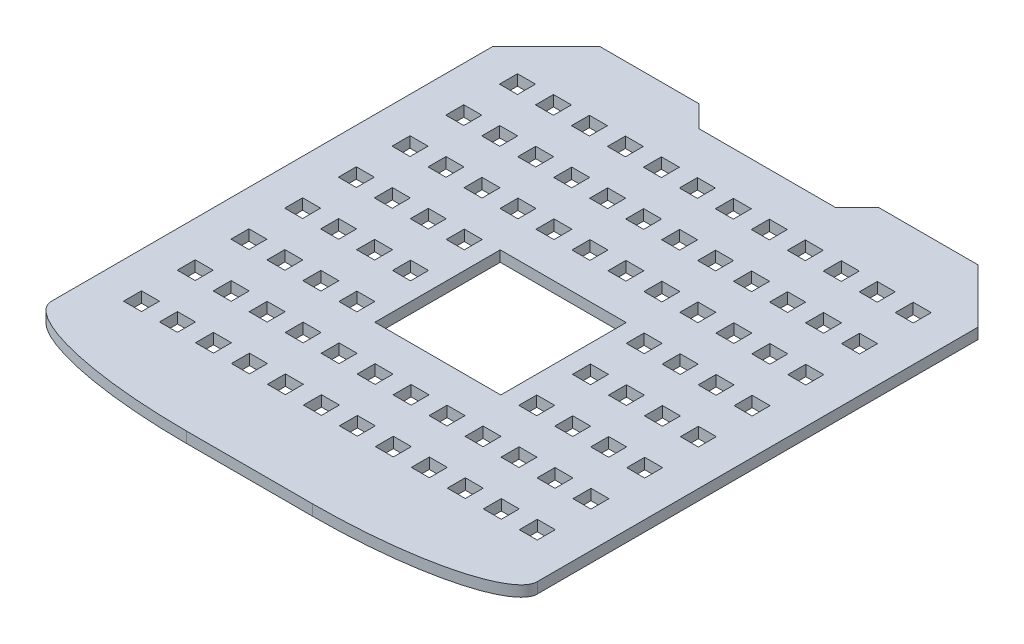
SolidWorks part; units mm, degrees
material "Balsa"
ref_plane "Front Plane" through (0, 0, 0) normal (0, 0, 1) x (1, 0, 0)
ref_plane "Top Plane" through (0, 0, 0) normal (0, 1, 0) x (1, 0, 0)
ref_plane "Right Plane" through (0, 0, 0) normal (1, 0, 0) x (0, 0, -1)
sketch "Sketch1" plane through (0, 0, 0) normal (0, 1, 0) x (1, 0, 0)
  line L1 (-67.5, 75) -> (67.5, 75)
  line L2 (-67.5, 75) -> (-67.5, -75)
  line L3 (-67.5, -75) -> (67.5, -75)
  line L4 (67.5, 75) -> (67.5, -75)
  line L5 (-67.5, 75) -> (67.5, -75) construction
  line L6 (-67.5, -75) -> (67.5, 75) construction
  point P0 (0, 0)
  dimension "D1" = 135
  dimension "D2" = 150
extrude "Boss-Extrude1" add sketch "Sketch1" along normal blind 3
sketch "Sketch2" plane through (0, 3, 0) normal (0, 1, 0) x (1, 0, 0)
  line L0 (-67.5, 75) -> (-67.5, -75) construction
  line L1 (-57.5, 52) -> (-52.5, 52)
  line L2 (-57.5, 52) -> (-57.5, 57)
  line L3 (-57.5, 57) -> (-52.5, 57)
  line L4 (-52.5, 52) -> (-52.5, 57)
  line L5 (-57.5, 52) -> (-52.5, 57) construction
  line L6 (-57.5, 57) -> (-52.5, 52) construction
  line L7 (67.5, 75) -> (-67.5, 75) construction
  line L732 (-47.5, 52) -> (-47.5, 57)
  line L733 (-47.5, 52) -> (-42.5, 52)
  line L734 (-42.5, 52) -> (-42.5, 57)
  line L735 (-47.5, 57) -> (-42.5, 57)
  line L736 (-37.5, 52) -> (-37.5, 57)
  line L737 (-37.5, 52) -> (-32.5, 52)
  line L738 (-32.5, 52) -> (-32.5, 57)
  line L739 (-37.5, 57) -> (-32.5, 57)
  line L740 (-27.5, 52) -> (-27.5, 57)
  line L741 (-27.5, 52) -> (-22.5, 52)
  line L742 (-22.5, 52) -> (-22.5, 57)
  line L743 (-27.5, 57) -> (-22.5, 57)
  line L744 (-17.5, 52) -> (-17.5, 57)
  line L745 (-17.5, 52) -> (-12.5, 52)
  line L746 (-12.5, 52) -> (-12.5, 57)
  line L747 (-17.5, 57) -> (-12.5, 57)
  line L748 (-7.5, 52) -> (-7.5, 57)
  line L749 (-7.5, 52) -> (-2.5, 52)
  line L750 (-2.5, 52) -> (-2.5, 57)
  line L751 (-7.5, 57) -> (-2.5, 57)
  line L752 (2.5, 52) -> (2.5, 57)
  line L753 (2.5, 52) -> (7.5, 52)
  line L754 (7.5, 52) -> (7.5, 57)
  line L755 (2.5, 57) -> (7.5, 57)
  line L756 (12.5, 52) -> (12.5, 57)
  line L757 (12.5, 52) -> (17.5, 52)
  line L758 (17.5, 52) -> (17.5, 57)
  line L759 (12.5, 57) -> (17.5, 57)
  line L760 (22.5, 52) -> (22.5, 57)
  line L761 (22.5, 52) -> (27.5, 52)
  line L762 (27.5, 52) -> (27.5, 57)
  line L763 (22.5, 57) -> (27.5, 57)
  line L764 (32.5, 52) -> (32.5, 57)
  line L765 (32.5, 52) -> (37.5, 52)
  line L766 (37.5, 52) -> (37.5, 57)
  line L767 (32.5, 57) -> (37.5, 57)
  line L768 (42.5, 52) -> (42.5, 57)
  line L769 (42.5, 52) -> (47.5, 52)
  line L770 (47.5, 52) -> (47.5, 57)
  line L771 (42.5, 57) -> (47.5, 57)
  line L772 (52.5, 52) -> (52.5, 57)
  line L773 (52.5, 52) -> (57.5, 52)
  line L774 (57.5, 52) -> (57.5, 57)
  line L775 (52.5, 57) -> (57.5, 57)
  line L780 (-47.5, 37.0714) -> (-47.5, 42.0714)
  line L781 (-47.5, 37.0714) -> (-42.5, 37.0714)
  line L782 (-42.5, 37.0714) -> (-42.5, 42.0714)
  line L783 (-47.5, 42.0714) -> (-42.5, 42.0714)
  line L784 (-37.5, 37.0714) -> (-37.5, 42.0714)
  line L785 (-37.5, 37.0714) -> (-32.5, 37.0714)
  line L786 (-32.5, 37.0714) -> (-32.5, 42.0714)
  line L787 (-37.5, 42.0714) -> (-32.5, 42.0714)
  line L788 (-27.5, 37.0714) -> (-27.5, 42.0714)
  line L789 (-27.5, 37.0714) -> (-22.5, 37.0714)
  line L790 (-22.5, 37.0714) -> (-22.5, 42.0714)
  line L791 (-27.5, 42.0714) -> (-22.5, 42.0714)
  line L792 (-17.5, 37.0714) -> (-17.5, 42.0714)
  line L793 (-17.5, 37.0714) -> (-12.5, 37.0714)
  line L794 (-12.5, 37.0714) -> (-12.5, 42.0714)
  line L795 (-17.5, 42.0714) -> (-12.5, 42.0714)
  line L796 (-7.5, 37.0714) -> (-7.5, 42.0714)
  line L797 (-7.5, 37.0714) -> (-2.5, 37.0714)
  line L798 (-2.5, 37.0714) -> (-2.5, 42.0714)
  line L799 (-7.5, 42.0714) -> (-2.5, 42.0714)
  line L800 (2.5, 37.0714) -> (2.5, 42.0714)
  line L801 (2.5, 37.0714) -> (7.5, 37.0714)
  line L802 (7.5, 37.0714) -> (7.5, 42.0714)
  line L803 (2.5, 42.0714) -> (7.5, 42.0714)
  line L804 (12.5, 37.0714) -> (12.5, 42.0714)
  line L805 (12.5, 37.0714) -> (17.5, 37.0714)
  line L806 (17.5, 37.0714) -> (17.5, 42.0714)
  line L807 (12.5, 42.0714) -> (17.5, 42.0714)
  line L808 (22.5, 37.0714) -> (22.5, 42.0714)
  line L809 (22.5, 37.0714) -> (27.5, 37.0714)
  line L810 (27.5, 37.0714) -> (27.5, 42.0714)
  line L811 (22.5, 42.0714) -> (27.5, 42.0714)
  line L812 (32.5, 37.0714) -> (32.5, 42.0714)
  line L813 (32.5, 37.0714) -> (37.5, 37.0714)
  line L814 (37.5, 37.0714) -> (37.5, 42.0714)
  line L815 (32.5, 42.0714) -> (37.5, 42.0714)
  line L816 (42.5, 37.0714) -> (42.5, 42.0714)
  line L817 (42.5, 37.0714) -> (47.5, 37.0714)
  line L818 (47.5, 37.0714) -> (47.5, 42.0714)
  line L819 (42.5, 42.0714) -> (47.5, 42.0714)
  line L820 (52.5, 37.0714) -> (52.5, 42.0714)
  line L821 (52.5, 37.0714) -> (57.5, 37.0714)
  line L822 (57.5, 37.0714) -> (57.5, 42.0714)
  line L823 (52.5, 42.0714) -> (57.5, 42.0714)
  line L828 (-47.5, 22.1429) -> (-47.5, 27.1429)
  line L829 (-47.5, 22.1429) -> (-42.5, 22.1429)
  line L830 (-42.5, 22.1429) -> (-42.5, 27.1429)
  line L831 (-47.5, 27.1429) -> (-42.5, 27.1429)
  line L832 (-37.5, 22.1429) -> (-37.5, 27.1429)
  line L833 (-37.5, 22.1429) -> (-32.5, 22.1429)
  line L834 (-32.5, 22.1429) -> (-32.5, 27.1429)
  line L835 (-37.5, 27.1429) -> (-32.5, 27.1429)
  line L836 (-27.5, 22.1429) -> (-27.5, 27.1429)
  line L837 (-27.5, 22.1429) -> (-22.5, 22.1429)
  line L838 (-22.5, 22.1429) -> (-22.5, 27.1429)
  line L839 (-27.5, 27.1429) -> (-22.5, 27.1429)
  line L840 (-17.5, 22.1429) -> (-17.5, 27.1429)
  line L841 (-17.5, 22.1429) -> (-12.5, 22.1429)
  line L842 (-12.5, 22.1429) -> (-12.5, 27.1429)
  line L843 (-17.5, 27.1429) -> (-12.5, 27.1429)
  line L844 (-7.5, 22.1429) -> (-7.5, 27.1429)
  line L845 (-7.5, 22.1429) -> (-2.5, 22.1429)
  line L846 (-2.5, 22.1429) -> (-2.5, 27.1429)
  line L847 (-7.5, 27.1429) -> (-2.5, 27.1429)
  line L848 (2.5, 22.1429) -> (2.5, 27.1429)
  line L849 (2.5, 22.1429) -> (7.5, 22.1429)
  line L850 (7.5, 22.1429) -> (7.5, 27.1429)
  line L851 (2.5, 27.1429) -> (7.5, 27.1429)
  line L852 (12.5, 22.1429) -> (12.5, 27.1429)
  line L853 (12.5, 22.1429) -> (17.5, 22.1429)
  line L854 (17.5, 22.1429) -> (17.5, 27.1429)
  line L855 (12.5, 27.1429) -> (17.5, 27.1429)
  line L856 (22.5, 22.1429) -> (22.5, 27.1429)
  line L857 (22.5, 22.1429) -> (27.5, 22.1429)
  line L858 (27.5, 22.1429) -> (27.5, 27.1429)
  line L859 (22.5, 27.1429) -> (27.5, 27.1429)
  line L860 (32.5, 22.1429) -> (32.5, 27.1429)
  line L861 (32.5, 22.1429) -> (37.5, 22.1429)
  line L862 (37.5, 22.1429) -> (37.5, 27.1429)
  line L863 (32.5, 27.1429) -> (37.5, 27.1429)
  line L864 (42.5, 22.1429) -> (42.5, 27.1429)
  line L865 (42.5, 22.1429) -> (47.5, 22.1429)
  line L866 (47.5, 22.1429) -> (47.5, 27.1429)
  line L867 (42.5, 27.1429) -> (47.5, 27.1429)
  line L868 (52.5, 22.1429) -> (52.5, 27.1429)
  line L869 (52.5, 22.1429) -> (57.5, 22.1429)
  line L870 (57.5, 22.1429) -> (57.5, 27.1429)
  line L871 (52.5, 27.1429) -> (57.5, 27.1429)
  line L876 (-47.5, 7.2143) -> (-47.5, 12.2143)
  line L877 (-47.5, 7.2143) -> (-42.5, 7.2143)
  line L878 (-42.5, 7.2143) -> (-42.5, 12.2143)
  line L879 (-47.5, 12.2143) -> (-42.5, 12.2143)
  line L880 (-37.5, 7.2143) -> (-37.5, 12.2143)
  line L881 (-37.5, 7.2143) -> (-32.5, 7.2143)
  line L882 (-32.5, 7.2143) -> (-32.5, 12.2143)
  line L883 (-37.5, 12.2143) -> (-32.5, 12.2143)
  line L884 (-27.5, 7.2143) -> (-27.5, 12.2143)
  line L885 (-27.5, 7.2143) -> (-22.5, 7.2143)
  line L886 (-22.5, 7.2143) -> (-22.5, 12.2143)
  line L887 (-27.5, 12.2143) -> (-22.5, 12.2143)
  line L888 (-17.5, 7.2143) -> (-17.5, 12.2143)
  line L889 (-17.5, 7.2143) -> (-12.5, 7.2143)
  line L890 (-12.5, 7.2143) -> (-12.5, 12.2143)
  line L891 (-17.5, 12.2143) -> (-12.5, 12.2143)
  line L892 (-7.5, 7.2143) -> (-7.5, 12.2143)
  line L893 (-7.5, 7.2143) -> (-2.5, 7.2143)
  line L894 (-2.5, 7.2143) -> (-2.5, 12.2143)
  line L895 (-7.5, 12.2143) -> (-2.5, 12.2143)
  line L896 (2.5, 7.2143) -> (2.5, 12.2143)
  line L897 (2.5, 7.2143) -> (7.5, 7.2143)
  line L898 (7.5, 7.2143) -> (7.5, 12.2143)
  line L899 (2.5, 12.2143) -> (7.5, 12.2143)
  line L900 (12.5, 7.2143) -> (12.5, 12.2143)
  line L901 (12.5, 7.2143) -> (17.5, 7.2143)
  line L902 (17.5, 7.2143) -> (17.5, 12.2143)
  line L903 (12.5, 12.2143) -> (17.5, 12.2143)
  line L904 (22.5, 7.2143) -> (22.5, 12.2143)
  line L905 (22.5, 7.2143) -> (27.5, 7.2143)
  line L906 (27.5, 7.2143) -> (27.5, 12.2143)
  line L907 (22.5, 12.2143) -> (27.5, 12.2143)
  line L908 (32.5, 7.2143) -> (32.5, 12.2143)
  line L909 (32.5, 7.2143) -> (37.5, 7.2143)
  line L910 (37.5, 7.2143) -> (37.5, 12.2143)
  line L911 (32.5, 12.2143) -> (37.5, 12.2143)
  line L912 (42.5, 7.2143) -> (42.5, 12.2143)
  line L913 (42.5, 7.2143) -> (47.5, 7.2143)
  line L914 (47.5, 7.2143) -> (47.5, 12.2143)
  line L915 (42.5, 12.2143) -> (47.5, 12.2143)
  line L916 (52.5, 7.2143) -> (52.5, 12.2143)
  line L917 (52.5, 7.2143) -> (57.5, 7.2143)
  line L918 (57.5, 7.2143) -> (57.5, 12.2143)
  line L919 (52.5, 12.2143) -> (57.5, 12.2143)
  line L924 (-47.5, -7.7143) -> (-47.5, -2.7143)
  line L925 (-47.5, -7.7143) -> (-42.5, -7.7143)
  line L926 (-42.5, -7.7143) -> (-42.5, -2.7143)
  line L927 (-47.5, -2.7143) -> (-42.5, -2.7143)
  line L928 (-37.5, -7.7143) -> (-37.5, -2.7143)
  line L929 (-37.5, -7.7143) -> (-32.5, -7.7143)
  line L930 (-32.5, -7.7143) -> (-32.5, -2.7143)
  line L931 (-37.5, -2.7143) -> (-32.5, -2.7143)
  line L932 (-27.5, -7.7143) -> (-27.5, -2.7143)
  line L933 (-27.5, -7.7143) -> (-22.5, -7.7143)
  line L934 (-22.5, -7.7143) -> (-22.5, -2.7143)
  line L935 (-27.5, -2.7143) -> (-22.5, -2.7143)
  line L936 (-17.5, -7.7143) -> (-17.5, -2.7143)
  line L937 (-17.5, -7.7143) -> (-12.5, -7.7143)
  line L938 (-12.5, -7.7143) -> (-12.5, -2.7143)
  line L939 (-17.5, -2.7143) -> (-12.5, -2.7143)
  line L940 (-7.5, -7.7143) -> (-7.5, -2.7143)
  line L941 (-7.5, -7.7143) -> (-2.5, -7.7143)
  line L942 (-2.5, -7.7143) -> (-2.5, -2.7143)
  line L943 (-7.5, -2.7143) -> (-2.5, -2.7143)
  line L944 (2.5, -7.7143) -> (2.5, -2.7143)
  line L945 (2.5, -7.7143) -> (7.5, -7.7143)
  line L946 (7.5, -7.7143) -> (7.5, -2.7143)
  line L947 (2.5, -2.7143) -> (7.5, -2.7143)
  line L948 (12.5, -7.7143) -> (12.5, -2.7143)
  line L949 (12.5, -7.7143) -> (17.5, -7.7143)
  line L950 (17.5, -7.7143) -> (17.5, -2.7143)
  line L951 (12.5, -2.7143) -> (17.5, -2.7143)
  line L952 (22.5, -7.7143) -> (22.5, -2.7143)
  line L953 (22.5, -7.7143) -> (27.5, -7.7143)
  line L954 (27.5, -7.7143) -> (27.5, -2.7143)
  line L955 (22.5, -2.7143) -> (27.5, -2.7143)
  line L956 (32.5, -7.7143) -> (32.5, -2.7143)
  line L957 (32.5, -7.7143) -> (37.5, -7.7143)
  line L958 (37.5, -7.7143) -> (37.5, -2.7143)
  line L959 (32.5, -2.7143) -> (37.5, -2.7143)
  line L960 (42.5, -7.7143) -> (42.5, -2.7143)
  line L961 (42.5, -7.7143) -> (47.5, -7.7143)
  line L962 (47.5, -7.7143) -> (47.5, -2.7143)
  line L963 (42.5, -2.7143) -> (47.5, -2.7143)
  line L964 (52.5, -7.7143) -> (52.5, -2.7143)
  line L965 (52.5, -7.7143) -> (57.5, -7.7143)
  line L966 (57.5, -7.7143) -> (57.5, -2.7143)
  line L967 (52.5, -2.7143) -> (57.5, -2.7143)
  line L972 (-47.5, -22.6429) -> (-47.5, -17.6429)
  line L973 (-47.5, -22.6429) -> (-42.5, -22.6429)
  line L974 (-42.5, -22.6429) -> (-42.5, -17.6429)
  line L975 (-47.5, -17.6429) -> (-42.5, -17.6429)
  line L976 (-37.5, -22.6429) -> (-37.5, -17.6429)
  line L977 (-37.5, -22.6429) -> (-32.5, -22.6429)
  line L978 (-32.5, -22.6429) -> (-32.5, -17.6429)
  line L979 (-37.5, -17.6429) -> (-32.5, -17.6429)
  line L980 (-27.5, -22.6429) -> (-27.5, -17.6429)
  line L981 (-27.5, -22.6429) -> (-22.5, -22.6429)
  line L982 (-22.5, -22.6429) -> (-22.5, -17.6429)
  line L983 (-27.5, -17.6429) -> (-22.5, -17.6429)
  line L984 (-17.5, -22.6429) -> (-17.5, -17.6429)
  line L985 (-17.5, -22.6429) -> (-12.5, -22.6429)
  line L986 (-12.5, -22.6429) -> (-12.5, -17.6429)
  line L987 (-17.5, -17.6429) -> (-12.5, -17.6429)
  line L988 (-7.5, -22.6429) -> (-7.5, -17.6429)
  line L989 (-7.5, -22.6429) -> (-2.5, -22.6429)
  line L990 (-2.5, -22.6429) -> (-2.5, -17.6429)
  line L991 (-7.5, -17.6429) -> (-2.5, -17.6429)
  line L992 (2.5, -22.6429) -> (2.5, -17.6429)
  line L993 (2.5, -22.6429) -> (7.5, -22.6429)
  line L994 (7.5, -22.6429) -> (7.5, -17.6429)
  line L995 (2.5, -17.6429) -> (7.5, -17.6429)
  line L996 (12.5, -22.6429) -> (12.5, -17.6429)
  line L997 (12.5, -22.6429) -> (17.5, -22.6429)
  line L998 (17.5, -22.6429) -> (17.5, -17.6429)
  line L999 (12.5, -17.6429) -> (17.5, -17.6429)
  line L1000 (22.5, -22.6429) -> (22.5, -17.6429)
  line L1001 (22.5, -22.6429) -> (27.5, -22.6429)
  line L1002 (27.5, -22.6429) -> (27.5, -17.6429)
  line L1003 (22.5, -17.6429) -> (27.5, -17.6429)
  line L1004 (32.5, -22.6429) -> (32.5, -17.6429)
  line L1005 (32.5, -22.6429) -> (37.5, -22.6429)
  line L1006 (37.5, -22.6429) -> (37.5, -17.6429)
  line L1007 (32.5, -17.6429) -> (37.5, -17.6429)
  line L1008 (42.5, -22.6429) -> (42.5, -17.6429)
  line L1009 (42.5, -22.6429) -> (47.5, -22.6429)
  line L1010 (47.5, -22.6429) -> (47.5, -17.6429)
  line L1011 (42.5, -17.6429) -> (47.5, -17.6429)
  line L1012 (52.5, -22.6429) -> (52.5, -17.6429)
  line L1013 (52.5, -22.6429) -> (57.5, -22.6429)
  line L1014 (57.5, -22.6429) -> (57.5, -17.6429)
  line L1015 (52.5, -17.6429) -> (57.5, -17.6429)
  line L1020 (-47.5, -37.5714) -> (-47.5, -32.5714)
  line L1021 (-47.5, -37.5714) -> (-42.5, -37.5714)
  line L1022 (-42.5, -37.5714) -> (-42.5, -32.5714)
  line L1023 (-47.5, -32.5714) -> (-42.5, -32.5714)
  line L1024 (-37.5, -37.5714) -> (-37.5, -32.5714)
  line L1025 (-37.5, -37.5714) -> (-32.5, -37.5714)
  line L1026 (-32.5, -37.5714) -> (-32.5, -32.5714)
  line L1027 (-37.5, -32.5714) -> (-32.5, -32.5714)
  line L1028 (-27.5, -37.5714) -> (-27.5, -32.5714)
  line L1029 (-27.5, -37.5714) -> (-22.5, -37.5714)
  line L1030 (-22.5, -37.5714) -> (-22.5, -32.5714)
  line L1031 (-27.5, -32.5714) -> (-22.5, -32.5714)
  line L1032 (-17.5, -37.5714) -> (-17.5, -32.5714)
  line L1033 (-17.5, -37.5714) -> (-12.5, -37.5714)
  line L1034 (-12.5, -37.5714) -> (-12.5, -32.5714)
  line L1035 (-17.5, -32.5714) -> (-12.5, -32.5714)
  line L1036 (-7.5, -37.5714) -> (-7.5, -32.5714)
  line L1037 (-7.5, -37.5714) -> (-2.5, -37.5714)
  line L1038 (-2.5, -37.5714) -> (-2.5, -32.5714)
  line L1039 (-7.5, -32.5714) -> (-2.5, -32.5714)
  line L1040 (2.5, -37.5714) -> (2.5, -32.5714)
  line L1041 (2.5, -37.5714) -> (7.5, -37.5714)
  line L1042 (7.5, -37.5714) -> (7.5, -32.5714)
  line L1043 (2.5, -32.5714) -> (7.5, -32.5714)
  line L1044 (12.5, -37.5714) -> (12.5, -32.5714)
  line L1045 (12.5, -37.5714) -> (17.5, -37.5714)
  line L1046 (17.5, -37.5714) -> (17.5, -32.5714)
  line L1047 (12.5, -32.5714) -> (17.5, -32.5714)
  line L1048 (22.5, -37.5714) -> (22.5, -32.5714)
  line L1049 (22.5, -37.5714) -> (27.5, -37.5714)
  line L1050 (27.5, -37.5714) -> (27.5, -32.5714)
  line L1051 (22.5, -32.5714) -> (27.5, -32.5714)
  line L1052 (32.5, -37.5714) -> (32.5, -32.5714)
  line L1053 (32.5, -37.5714) -> (37.5, -37.5714)
  line L1054 (37.5, -37.5714) -> (37.5, -32.5714)
  line L1055 (32.5, -32.5714) -> (37.5, -32.5714)
  line L1056 (42.5, -37.5714) -> (42.5, -32.5714)
  line L1057 (42.5, -37.5714) -> (47.5, -37.5714)
  line L1058 (47.5, -37.5714) -> (47.5, -32.5714)
  line L1059 (42.5, -32.5714) -> (47.5, -32.5714)
  line L1060 (52.5, -37.5714) -> (52.5, -32.5714)
  line L1061 (52.5, -37.5714) -> (57.5, -37.5714)
  line L1062 (57.5, -37.5714) -> (57.5, -32.5714)
  line L1063 (52.5, -32.5714) -> (57.5, -32.5714)
  line L1068 (-47.5, -52.5) -> (-47.5, -47.5)
  line L1069 (-47.5, -52.5) -> (-42.5, -52.5)
  line L1070 (-42.5, -52.5) -> (-42.5, -47.5)
  line L1071 (-47.5, -47.5) -> (-42.5, -47.5)
  line L1072 (-37.5, -52.5) -> (-37.5, -47.5)
  line L1073 (-37.5, -52.5) -> (-32.5, -52.5)
  line L1074 (-32.5, -52.5) -> (-32.5, -47.5)
  line L1075 (-37.5, -47.5) -> (-32.5, -47.5)
  line L1076 (-27.5, -52.5) -> (-27.5, -47.5)
  line L1077 (-27.5, -52.5) -> (-22.5, -52.5)
  line L1078 (-22.5, -52.5) -> (-22.5, -47.5)
  line L1079 (-27.5, -47.5) -> (-22.5, -47.5)
  line L1080 (-17.5, -52.5) -> (-17.5, -47.5)
  line L1081 (-17.5, -52.5) -> (-12.5, -52.5)
  line L1082 (-12.5, -52.5) -> (-12.5, -47.5)
  line L1083 (-17.5, -47.5) -> (-12.5, -47.5)
  line L1084 (-7.5, -52.5) -> (-7.5, -47.5)
  line L1085 (-7.5, -52.5) -> (-2.5, -52.5)
  line L1086 (-2.5, -52.5) -> (-2.5, -47.5)
  line L1087 (-7.5, -47.5) -> (-2.5, -47.5)
  line L1088 (2.5, -52.5) -> (2.5, -47.5)
  line L1089 (2.5, -52.5) -> (7.5, -52.5)
  line L1090 (7.5, -52.5) -> (7.5, -47.5)
  line L1091 (2.5, -47.5) -> (7.5, -47.5)
  line L1092 (12.5, -52.5) -> (12.5, -47.5)
  line L1093 (12.5, -52.5) -> (17.5, -52.5)
  line L1094 (17.5, -52.5) -> (17.5, -47.5)
  line L1095 (12.5, -47.5) -> (17.5, -47.5)
  line L1096 (22.5, -52.5) -> (22.5, -47.5)
  line L1097 (22.5, -52.5) -> (27.5, -52.5)
  line L1098 (27.5, -52.5) -> (27.5, -47.5)
  line L1099 (22.5, -47.5) -> (27.5, -47.5)
  line L1100 (32.5, -52.5) -> (32.5, -47.5)
  line L1101 (32.5, -52.5) -> (37.5, -52.5)
  line L1102 (37.5, -52.5) -> (37.5, -47.5)
  line L1103 (32.5, -47.5) -> (37.5, -47.5)
  line L1104 (42.5, -52.5) -> (42.5, -47.5)
  line L1105 (42.5, -52.5) -> (47.5, -52.5)
  line L1106 (47.5, -52.5) -> (47.5, -47.5)
  line L1107 (42.5, -47.5) -> (47.5, -47.5)
  line L1108 (52.5, -52.5) -> (52.5, -47.5)
  line L1109 (52.5, -52.5) -> (57.5, -52.5)
  line L1110 (57.5, -52.5) -> (57.5, -47.5)
  line L1111 (52.5, -47.5) -> (57.5, -47.5)
  line L1116 (-57.5, 37.0714) -> (-57.5, 42.0714)
  line L1117 (-57.5, 37.0714) -> (-52.5, 37.0714)
  line L1118 (-52.5, 37.0714) -> (-52.5, 42.0714)
  line L1119 (-57.5, 42.0714) -> (-52.5, 42.0714)
  line L1120 (-57.5, 22.1429) -> (-57.5, 27.1429)
  line L1121 (-57.5, 22.1429) -> (-52.5, 22.1429)
  line L1122 (-52.5, 22.1429) -> (-52.5, 27.1429)
  line L1123 (-57.5, 27.1429) -> (-52.5, 27.1429)
  line L1124 (-57.5, 7.2143) -> (-57.5, 12.2143)
  line L1125 (-57.5, 7.2143) -> (-52.5, 7.2143)
  line L1126 (-52.5, 7.2143) -> (-52.5, 12.2143)
  line L1127 (-57.5, 12.2143) -> (-52.5, 12.2143)
  line L1128 (-57.5, -7.7143) -> (-57.5, -2.7143)
  line L1129 (-57.5, -7.7143) -> (-52.5, -7.7143)
  line L1130 (-52.5, -7.7143) -> (-52.5, -2.7143)
  line L1131 (-57.5, -2.7143) -> (-52.5, -2.7143)
  line L1132 (-57.5, -22.6429) -> (-57.5, -17.6429)
  line L1133 (-57.5, -22.6429) -> (-52.5, -22.6429)
  line L1134 (-52.5, -22.6429) -> (-52.5, -17.6429)
  line L1135 (-57.5, -17.6429) -> (-52.5, -17.6429)
  line L1136 (-57.5, -37.5714) -> (-57.5, -32.5714)
  line L1137 (-57.5, -37.5714) -> (-52.5, -37.5714)
  line L1138 (-52.5, -37.5714) -> (-52.5, -32.5714)
  line L1139 (-57.5, -32.5714) -> (-52.5, -32.5714)
  line L1140 (-57.5, -52.5) -> (-57.5, -47.5)
  line L1141 (-57.5, -52.5) -> (-52.5, -52.5)
  line L1142 (-52.5, -52.5) -> (-52.5, -47.5)
  line L1143 (-57.5, -47.5) -> (-52.5, -47.5)
  line L1144 (-42, 75) -> (-42, -75) construction
  line L1145 (-67.5, -75) -> (67.5, -75) construction
  line L1147 (62.5, 52) -> (62.5, 57) [skipped]
  line L1148 (62.5, 52) -> (67.5, 52) [skipped]
  line L1149 (67.5, 52) -> (67.5, 57) [skipped]
  line L1150 (62.5, 57) -> (67.5, 57) [skipped]
  line L1151 (62.5, 37.0714) -> (62.5, 42.0714) [skipped]
  line L1152 (62.5, 37.0714) -> (67.5, 37.0714) [skipped]
  line L1153 (67.5, 37.0714) -> (67.5, 42.0714) [skipped]
  line L1154 (62.5, 42.0714) -> (67.5, 42.0714) [skipped]
  line L1155 (62.5, 22.1429) -> (62.5, 27.1429) [skipped]
  line L1156 (62.5, 22.1429) -> (67.5, 22.1429) [skipped]
  line L1157 (67.5, 22.1429) -> (67.5, 27.1429) [skipped]
  line L1158 (62.5, 27.1429) -> (67.5, 27.1429) [skipped]
  line L1159 (62.5, 7.2143) -> (62.5, 12.2143) [skipped]
  line L1160 (62.5, 7.2143) -> (67.5, 7.2143) [skipped]
  line L1161 (67.5, 7.2143) -> (67.5, 12.2143) [skipped]
  line L1162 (62.5, 12.2143) -> (67.5, 12.2143) [skipped]
  line L1163 (62.5, -7.7143) -> (62.5, -2.7143) [skipped]
  line L1164 (62.5, -7.7143) -> (67.5, -7.7143) [skipped]
  line L1165 (67.5, -7.7143) -> (67.5, -2.7143) [skipped]
  line L1166 (62.5, -2.7143) -> (67.5, -2.7143) [skipped]
  line L1167 (62.5, -22.6429) -> (62.5, -17.6429) [skipped]
  line L1168 (62.5, -22.6429) -> (67.5, -22.6429) [skipped]
  line L1169 (67.5, -22.6429) -> (67.5, -17.6429) [skipped]
  line L1170 (62.5, -17.6429) -> (67.5, -17.6429) [skipped]
  line L1171 (62.5, -37.5714) -> (62.5, -32.5714) [skipped]
  line L1172 (62.5, -37.5714) -> (67.5, -37.5714) [skipped]
  line L1173 (67.5, -37.5714) -> (67.5, -32.5714) [skipped]
  line L1174 (62.5, -32.5714) -> (67.5, -32.5714) [skipped]
  line L1175 (62.5, -52.5) -> (62.5, -47.5) [skipped]
  line L1176 (62.5, -52.5) -> (67.5, -52.5) [skipped]
  line L1177 (67.5, -52.5) -> (67.5, -47.5) [skipped]
  line L1178 (62.5, -47.5) -> (67.5, -47.5) [skipped]
  point P0 (-55, 54.5)
  dimension "D1" = 5
  dimension "D2" = 8
  dimension "D3" = 10
  dimension "D4" = 23
  dimension "D6" = 13
  dimension "D5" = 25.5
  dimension "D7" = 22.5
extrude "Cut-Extrude1" cut sketch "Sketch2" against normal through all
fillet "Fillet1" radius 12.5 1 edges at (-67.5, 1.5, 75) second distance 50 first distance on face at (-67.5, 1.5, 0)
fillet "Fillet2" radius 12.5 1 edges at (67.5, 1.5, 75) second distance 50 first distance on face at (67.5, 1.5, 0)
sketch "Sketch4" plane through (0, 3, 0) normal (0, 1, 0) x (1, 0, 0)
  line L0 (-67.5, 60) -> (-67.5, 75)
  line L1 (-67.5, 75) -> (-67.5, -62.5) construction
  line L2 (-67.5, 75) -> (-52.5, 75)
  line L3 (67.5, 75) -> (-67.5, 75) construction
  line L4 (-52.5, 75) -> (-67.5, 60)
  line L5 (0, 75) -> (0, -75) construction
  line L6 (-17.5, -75) -> (17.5, -75) construction
  line L7 (67.5, 75) -> (52.5, 75)
  line L8 (67.5, 60) -> (67.5, 75)
  line L9 (52.5, 75) -> (67.5, 60)
  dimension "D1" = 45
  dimension "D2" = 15
extrude "Cut-Extrude2" cut sketch "Sketch4" against normal through all
sketch "Sketch5" plane through (0, 3, 0) normal (0, 1, 0) x (1, 0, 0)
  line L6 (0, -75) -> (0, 75) construction
  line L7 (-17.5, -75) -> (17.5, -75) construction
  line L8 (52.5, 75) -> (-52.5, 75) construction
  line L9 (-25, 75) -> (25, 75)
  line L11 (-19, 69) -> (19, 69)
  line L13 (-25, 75) -> (9.8447, 59.8447) construction
  line L14 (-9.8447, 59.8447) -> (25, 75) construction
  line L15 (-25, 75) -> (-19, 69)
  line L16 (25, 75) -> (19, 69)
  point P0 (0, 64.1266)
  point P1 (0, 75)
  dimension "D1" = 50
  dimension "D2" = 45
  dimension "D3" = 6
extrude "Cut-Extrude3" cut sketch "Sketch5" against normal through all
sketch "Sketch6" plane through (0, 3, 0) normal (0, 1, 0) x (1, 0, 0)
  line L9 (-17.5, -22.6429) -> (17.5, -22.6429)
  line L10 (-17.5, -22.6429) -> (-17.5, 12.2143)
  line L11 (-17.5, 12.2143) -> (17.5, 12.2143)
  line L12 (17.5, -22.6429) -> (17.5, 12.2143)
extrude "Cut-Extrude4" cut sketch "Sketch6" against normal through all
